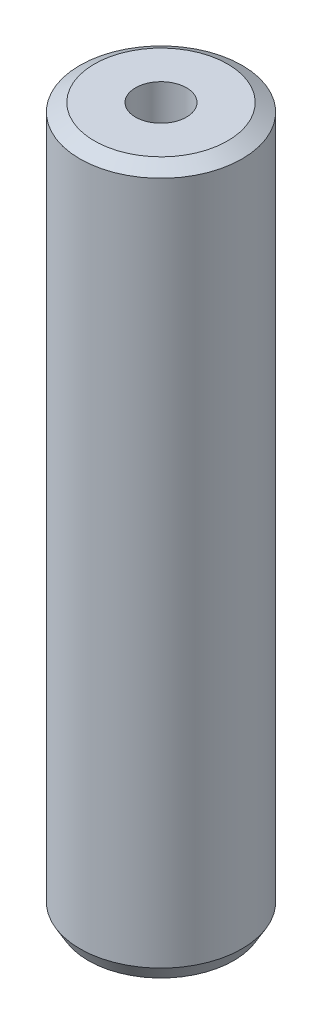
SolidWorks part; units mm, degrees
ref_plane "Front Plane" through (0, 0, 0) normal (0, 0, 1) x (1, 0, 0)
ref_plane "Top Plane" through (0, 0, 0) normal (0, 1, 0) x (1, 0, 0)
ref_plane "Right Plane" through (0, 0, 0) normal (1, 0, 0) x (0, 0, -1)
sketch "Sketch1" plane through (0, 0, 0) normal (0, 1, 0) x (1, 0, 0)
  circle A0 centre (0, 0) radius 27.5
  dimension "SHAFT_OD" = 55
extrude "Boss-Extrude1" add sketch "Sketch1" along normal blind 239.6798
sketch "Sketch2" plane through (0, 0, 0) normal (0, 1, 0) x (1, 0, 0)
  circle A0 centre (0, 0) radius 8.6386
  dimension "BORE_D" = 17.2773
extrude "Cut-Extrude1" cut sketch "Sketch2" along normal through all
chamfer "Chamfer1" distance 2.8324 angle 60 2 edges at (0, 239.6798, 27.5) (0, 0, 27.5) first distance on face at (0, 239.6798, 27.5) first distance on face at (0, 0, 8.6386)
